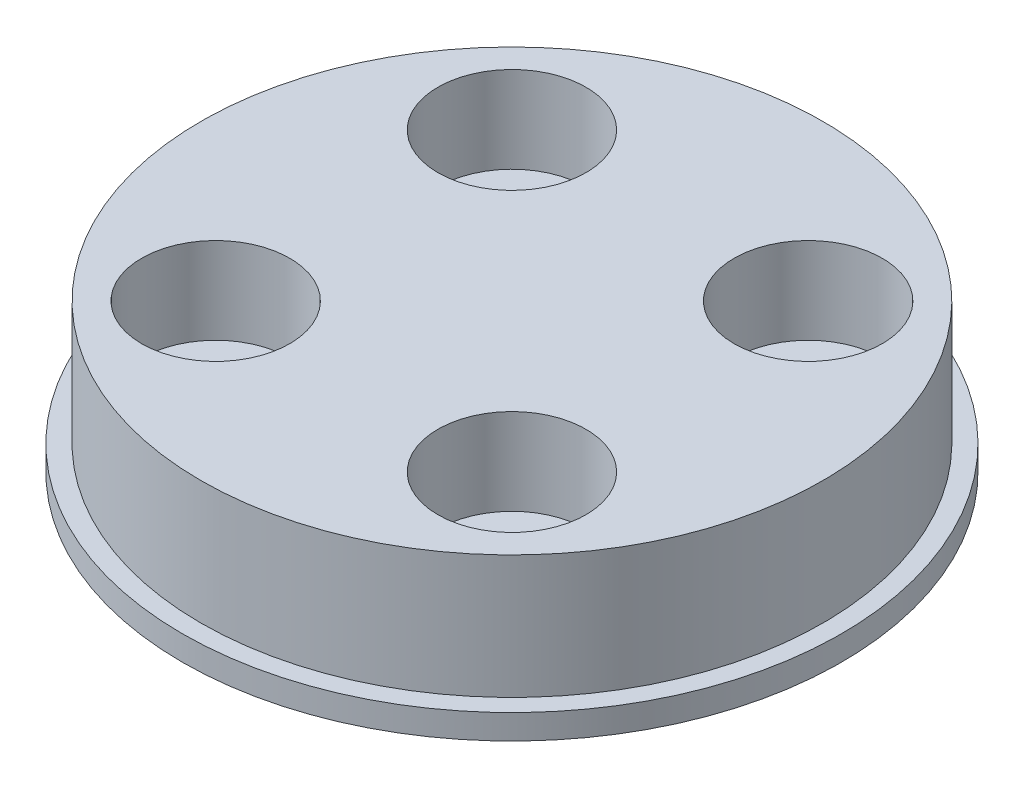
SolidWorks part; units mm, degrees
material "ABS"
ref_plane "Front Plane" through (0, 0, 0) normal (0, 0, 1) x (1, 0, 0)
ref_plane "Top Plane" through (0, 0, 0) normal (0, 1, 0) x (1, 0, 0)
ref_plane "Right Plane" through (0, 0, 0) normal (1, 0, 0) x (0, 0, -1)
sketch "Sketch1" plane through (0, 33, 0) normal (0, 1, 0) x (1, 0, 0)
  circle A0 centre (0, 0) radius 12.6
  circle A1 centre (0, 0) radius 13.35
  circle A2 centre (-6, 6) radius 1.575
  circle A3 centre (6, 6) radius 1.575
  circle A4 centre (6, -6) radius 1.575
  circle A5 centre (-6, -6) radius 1.575
  point P7 (0, 0)
  point P8 (-4.7832, -6.0586)
  point P9 (0, 0)
  point P16 (0, 0)
  circle M2 centre (-6, -6) radius 1.575
  circle M3 centre (6, -6) radius 1.575
  circle M4 centre (6, 6) radius 1.575
  circle M5 centre (-6, 6) radius 1.575
  dimension "D1" = 3.15
  dimension "D3" = 25.2
  dimension "D4" = 26.7
  dimension "D2" = 4
extrude "Boss-Extrude1" add sketch "Sketch1" along normal blind 1 contours A0 M3 M5 M4 M2 | A1 A0 region at (0, 33, 0) region at (-12.9724, 33, 0)
extrude "Boss-Extrude2" add sketch "Sketch1<3>" along normal blind 6 contours A0 M3 M5 M4 M2 region at (0, 33, 0)
sketch "Sketch1<3>" plane through (0, 33, 0) normal (0, 1, 0) x (1, 0, 0) same geometry as "Sketch1"
sketch "Sketch2" plane through (0, 39, 0) normal (0, 1, 0) x (1, 0, 0)
  circle A0 centre (-6, 6) radius 3
  circle A1 centre (6, 6) radius 3
  circle A2 centre (6, -6) radius 3
  circle A3 centre (-6, -6) radius 3
  point P3 (0, 0)
  point P4 (0, 0)
  point P5 (-6, -6)
  point P12 (0, 0)
  dimension "D1" = 6
  dimension "D2" = 4
extrude "Cut-Extrude1" cut sketch "Sketch2" against normal blind 3.5
equation "\"RingPinShaft\"= 5.05"
equation "\"CenterBearingOut\"=32.05"
equation "\"OutputBearingOut\"=37.05"
equation "\"RingPostIn\"=5.15"
equation "\"CamBearingOut\"=15.1"
equation "\"DiskOutputShaft\"=10.1"
equation "\"CenterShaft\"=25.2"
equation "\"Eccentricity\"=2"
equation "\"CycCamShaft\"=10.05"
equation "\"m3Thru\"=3.15"
equation "\"m3Insert\"=4.2"
equation "\"D1@Sketch1\"=\"m3Thru\""
equation "\"D3@Sketch1\"=\"CenterShaft\""
equation "\"D4@Sketch1\"=\"CenterShaft\"+1.5"
